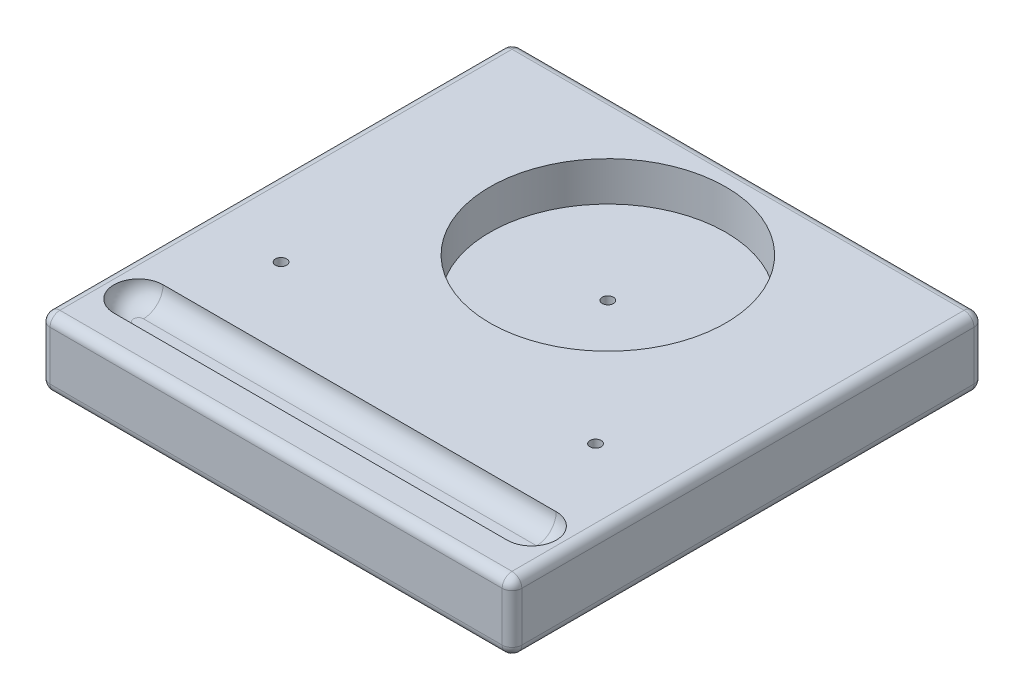
SolidWorks part; units mm, degrees
ref_plane "Front Plane" through (0, 0, 0) normal (0, 0, 1) x (1, 0, 0)
ref_plane "Top Plane" through (0, 0, 0) normal (0, 1, 0) x (1, 0, 0)
ref_plane "Right Plane" through (0, 0, 0) normal (1, 0, 0) x (0, 0, -1)
sketch "Sketch1" plane through (0, 0, 0) normal (0, 0, 1) x (1, 0, 0)
  line L7 (-76.2, -11.1125) -> (76.2, -11.1125)
  line L8 (-76.2, -11.1125) -> (-76.2, 11.1125)
  line L9 (-76.2, 11.1125) -> (76.2, 11.1125)
  line L10 (76.2, -11.1125) -> (76.2, 11.1125)
  line L11 (-76.2, -11.1125) -> (76.2, 11.1125) construction
  line L12 (-76.2, 11.1125) -> (76.2, -11.1125) construction
  point P4 (0, 0)
  point P14 (0, 0)
  dimension "Thickness" = 22.225
  dimension "Width" = 152.4
sketch "Sketch2" plane through (0, 0, 0) normal (0, 1, 0) x (0, 0, -1)
  line L0 (76.2, 76.2) -> (-76.2, 76.2) construction
  point P4 (0, 76.2)
  dimension "Length" = 152.4
sketch "Sketch3" plane through (0, 0, 0) normal (0, 0, 1) x (1, 0, 0)
  line L6 (-76.2, 11.1125) -> (76.2, 11.1125)
  line L7 (76.2, 11.1125) -> (76.2, -11.1125)
  line L8 (76.2, -11.1125) -> (-76.2, -11.1125)
  line L9 (-76.2, -11.1125) -> (-76.2, 11.1125)
extrude "Boss-Extrude1" add sketch "Sketch3" along normal mid plane 152.4
sketch "Feet" plane through (0, -11.1125, 0) normal (0, -1, 0) x (1, 0, 0)
  line L0 (-76.2, 76.2) -> (76.2, 76.2) construction
  line L1 (-76.2, 76.2) -> (-76.2, -76.2) construction
  line L2 (0, 76.2) -> (0, -76.2) construction
  line L3 (-76.2, -76.2) -> (76.2, -76.2) construction
  line L4 (-76.2, 0) -> (76.2, 0) construction
  line L5 (76.2, 76.2) -> (76.2, -76.2) construction
  circle A0 centre (-63.5, 63.5) radius 6.35
  circle A1 centre (63.5, 63.5) radius 6.35
  circle A2 centre (63.5, -63.5) radius 6.35
  circle A3 centre (-63.5, -63.5) radius 6.35
  dimension "D3" = 12.7
  dimension "D1" = 12.7
  dimension "D2" = 12.7
extrude "Rubber Feet" cut sketch "Feet" against normal blind 3.175
sketch "Sketch6" plane through (0, 11.1125, 0) normal (0, 1, 0) x (1, 0, 0)
  line L0 (-76.2, -76.2) -> (-76.2, -57.15) construction
  line L1 (-76.2, -76.2) -> (-76.2, 76.2) construction
  line L2 (-76.2, -57.15) -> (-63.5, -57.15) construction
  line L3 (-63.5, -57.15) -> (63.5, -57.15) construction
  line L4 (-63.5, -49.2125) -> (63.5, -49.2125)
  line L5 (-63.5, -65.0875) -> (63.5, -65.0875)
  line L6 (0, -57.15) -> (0, -76.2) construction
  line L7 (76.2, -76.2) -> (-76.2, -76.2) construction
  arc A0 (-63.5, -49.2125) -> (-63.5, -65.0875) centre (-63.5, -57.15) ccw
  arc A1 (63.5, -65.0875) -> (63.5, -49.2125) centre (63.5, -57.15) ccw
  point P5 (0, -57.15)
  dimension "D1" = 19.05
  dimension "D3" = 15.875
extrude "Cut-Extrude2" cut sketch "Sketch6" against normal blind 6.35
fillet "Fillet2" radius 6.35 4 edges at (0, 4.7625, 49.2125) (71.4375, 4.7625, 57.15) (0, 4.7625, 65.0875) (-71.4375, 4.7625, 57.15)
fillet "Fillet1" radius 3.175 12 edges at (-76.2, 0, -76.2) (76.2, 0, -76.2) (76.2, 0, 76.2) (-76.2, 0, 76.2) (-76.2, -11.1125, 0) (0, -11.1125, 76.2) (76.2, -11.1125, 0) (0, -11.1125, -76.2) (76.2, 11.1125, 0) (0, 11.1125, 76.2) (-76.2, 11.1125, 0) (0, 11.1125, -76.2)
sketch "Sketch7" plane through (0, -11.1125, 0) normal (0, -1, 0) x (1, 0, 0)
  line L0 (-69.85, 23.8125) -> (69.85, 23.8125) construction
  line L1 (0, 11.1125) -> (0, 36.5125) construction
  line L2 (-50.8, 23.8125) -> (50.8, 23.8125) construction
  line L4 (73.025, 73.025) -> (-73.025, 73.025)
  line L5 (-73.025, 73.025) -> (-73.025, -73.025)
  line L6 (-73.025, -73.025) -> (73.025, -73.025)
  line L7 (73.025, -73.025) -> (73.025, 73.025)
  line L8 (73.025, 73.025) -> (-73.025, 73.025)
  line L9 (-73.025, 73.025) -> (-73.025, -73.025)
  line L10 (-73.025, -73.025) -> (73.025, -73.025)
  line L11 (73.025, -73.025) -> (73.025, 73.025)
  line L12 (69.85, 36.5125) -> (-69.85, 36.5125)
  line L13 (69.85, 11.1125) -> (69.85, 36.5125)
  line L14 (-69.85, 11.1125) -> (69.85, 11.1125)
  line L15 (-69.85, 36.5125) -> (-69.85, 11.1125)
  line L16 (69.85, 36.5125) -> (-69.85, 36.5125)
  line L17 (69.85, 11.1125) -> (69.85, 36.5125)
  line L18 (-69.85, 11.1125) -> (69.85, 11.1125)
  line L19 (-69.85, 36.5125) -> (-69.85, 11.1125)
  point P11 (0, 0)
  point P18 (0, 23.8125)
  dimension "D3" = 101.6
  dimension "D1" = 0
  dimension "D2" = 0
hole_wizard "CBORE for M3 Hex Socket Head Cap Screw1" positions "Sketch8" profile "Sketch9" counterbore size "M3" standard "DIN" end condition through all
sketch "Sketch8" plane through (0, -11.1125, 0) normal (0, -1, 0) x (-1, 0, 0)
  point P0 (-50.8, -23.8125)
  point P3 (50.8, -23.8125)
sketch "Sketch9" plane through (50.8, -11.1125, 23.8125) normal (1, 0, 0) x (0, 0, -1)
  line L0 (0, 0) -> (0, 22.225)
  line L1 (0, 22.225) -> (1.8, 22.225)
  line L3 (1.8, 22.225) -> (1.8, 3.4)
  line L4 (1.8, 3.4) -> (3.25, 3.4)
  line L5 (3.25, 3.4) -> (3.25, 0)
  line L7 (3.25, 0) -> (0, 0)
  line L11 (0, -6.35) -> (0, 107.95) construction
  dimension "Thru Hole Dia." = 3.6
  dimension "Thru Hole Depth" = 22.225
  dimension "C'Bore Dia." = 6.5
  dimension "C'Bore Depth" = 3.4
sketch "Sketch10" plane through (0, 11.1125, 0) normal (0, 1, 0) x (1, 0, 0)
  line L0 (-69.85, -11.1125) -> (-69.85, 73.025) construction
  line L1 (-73.025, 73.025) -> (73.025, 73.025) construction
  line L2 (-69.85, 30.9562) -> (0, 30.9562) construction
  circle A0 centre (0, 30.9562) radius 38.1
  dimension "D1" = 76.2
extrude "Cut-Extrude3" cut sketch "Sketch10" against normal blind 12.7
sketch "Sketch11" plane through (0, -11.1125, 0) normal (0, -1, 0) x (1, 0, 0)
  line L4 (73.025, 73.025) -> (-73.025, 73.025)
  line L5 (-73.025, 73.025) -> (-73.025, -73.025)
  line L6 (-73.025, -73.025) -> (73.025, -73.025)
  line L7 (73.025, -73.025) -> (73.025, 73.025)
  line L8 (73.025, 73.025) -> (-73.025, 73.025)
  line L9 (-73.025, 73.025) -> (-73.025, -73.025)
  line L10 (-73.025, -73.025) -> (73.025, -73.025)
  line L11 (73.025, -73.025) -> (73.025, 73.025)
  circle A1 centre (0, -30.9562) radius 38.1
  circle A2 centre (0, -30.9562) radius 38.1
  dimension "D1" = 0
  dimension "D2" = 0
hole_wizard "CBORE for M3 Hex Socket Head Cap Screw2" positions "Sketch12" profile "Sketch13" counterbore size "M3" standard "DIN" end condition through all
sketch "Sketch12" plane through (0, -11.1125, 0) normal (0, -1, 0) x (-1, 0, 0)
  point P0 (0, 30.9562)
sketch "Sketch13" plane through (0, -11.1125, -30.9562) normal (1, 0, 0) x (0, 0, -1)
  line L0 (0, 0) -> (0, 22.225)
  line L1 (0, 22.225) -> (1.8, 22.225)
  line L3 (1.8, 22.225) -> (1.8, 3.4)
  line L4 (3.25, 3.4) -> (1.8, 3.4)
  line L5 (3.25, 3.4) -> (3.25, 0.025)
  line L6 (3.25, 0.025) -> (3.275, 0)
  line L7 (3.275, 0) -> (0, 0)
  line L8 (-3.25, 0.025) -> (-3.275, 0) construction
  line L11 (0, -6.35) -> (0, 107.95) construction
  dimension "Thru Hole Dia." = 3.6
  dimension "Thru Hole Depth" = 22.225
  dimension "C'Bore Dia." = 6.5
  dimension "C'Bore Depth" = 3.4
  dimension "Near C'Sink Dia." = 6.55
  dimension "Near C'Sink Angle" = 90
equation "\"D1@Boss-Extrude1\" = \"Length@Sketch2\""
